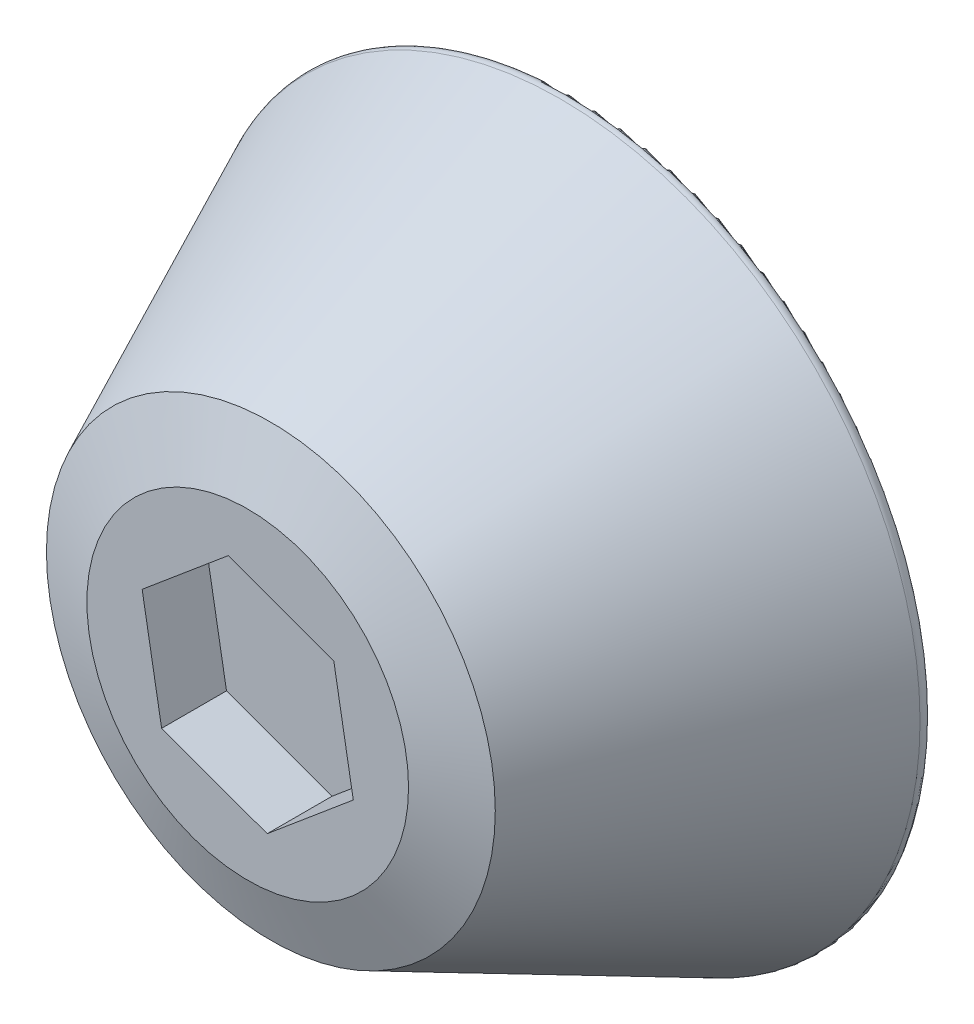
SolidWorks part; units mm, degrees
ref_plane "Front Plane" through (0, 0, 0) normal (0, 0, 1) x (1, 0, 0)
ref_plane "Top Plane" through (0, 0, 0) normal (0, 1, 0) x (1, 0, 0)
ref_plane "Right Plane" through (0, 0, 0) normal (1, 0, 0) x (0, 0, -1)
sketch "Sketch1" plane through (0, 0, 0) normal (0, 0, 1) x (1, 0, 0)
  circle A0 centre (0, 0) radius 28.575
  dimension "D1" = 57.15
extrude "Cone Extrude" add sketch "Sketch1" along normal blind 25.4 draft 25
sketch "Sketch2" plane through (0, 0, 0) normal (0, 0, -1) x (-1, 0, 0)
  line L0 (-2.0599, 2.35) -> (2.0599, 2.35)
  arc A0 (-2.0599, 2.35) -> (2.0599, 2.35) centre (0, 0) ccw
  dimension "D1" = 6.25
  dimension "D2" = 2.35
extrude "Motor Axle Cut" cut sketch "Sketch2" against normal blind 15.25
chamfer "Chamfer1" distance 2 angle 45 1 edges at (16.7308, 0, 25.4) first distance on face at (16.7308, 0, 25.4)
chamfer "Chamfer2" distance 2 angle 45 2 edges at (0, 2.35, 0) (0, -3.125, 0)
sketch "Sketch3" plane through (0, 0, 25.4) normal (0, 0, 1) x (1, 0, 0)
  line L1 (6.7416, 5.6542) -> (-1.5259, 8.6655)
  line L2 (-1.5259, 8.6655) -> (-8.2675, 3.0113)
  line L3 (-8.2675, 3.0113) -> (-6.7416, -5.6542)
  line L4 (-6.7416, -5.6542) -> (1.5259, -8.6655)
  line L5 (1.5259, -8.6655) -> (8.2675, -3.0113)
  line L6 (8.2675, -3.0113) -> (6.7416, 5.6542)
  circle A0 centre (0, 0) radius 7.62 construction
  dimension "D1" = 15.24
extrude "Bolt Hole Cut" cut sketch "Sketch3" against normal blind 5.08
fillet "Fillet1" radius 0.635 1 edges at (28.575, 0, 0)
